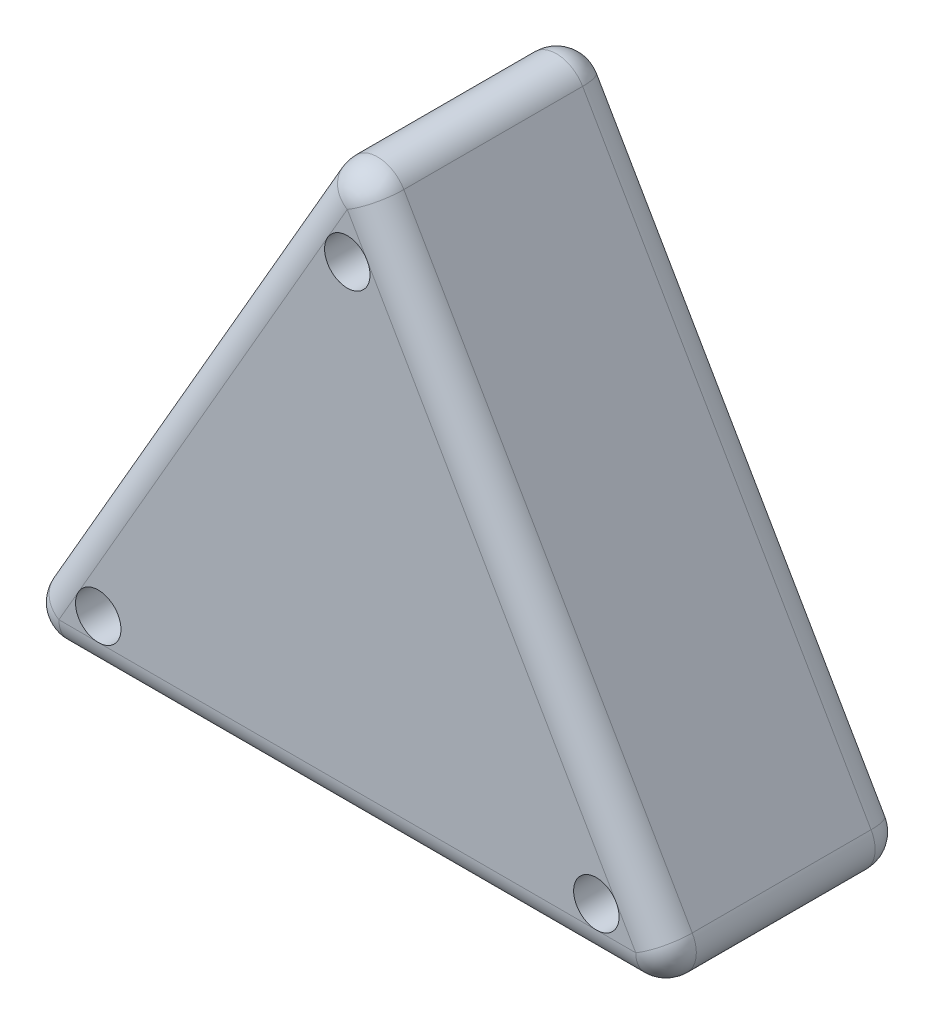
SolidWorks part; units mm, degrees
ref_plane "Plan de face" through (0, 0, 0) normal (0, 0, 1) x (1, 0, 0)
ref_plane "Plan de dessus" through (0, 0, 0) normal (0, 1, 0) x (1, 0, 0)
ref_plane "Plan de droite" through (0, 0, 0) normal (1, 0, 0) x (0, 0, -1)
sketch "Esquisse1" plane through (0, 0, 0) normal (0, 0, 1) x (1, 0, 0)
  line L0 (1.7321, 3) -> (20.7679, 35.9711)
  line L1 (3.4641, 0) -> (41.5359, 0)
  line L2 (24.2321, 35.9711) -> (43.2679, 3)
  line L3 (43.2679, 1) -> (31.5561, 7.7618) construction
  line L4 (22.5, 3.8637) -> (22.5, -6.3721) construction
  arc A0 (41.5359, 0) -> (43.2679, 3) centre (41.5359, 2) ccw
  arc A1 (1.7321, 3) -> (3.4641, 0) centre (3.4641, 2) ccw
  arc A2 (20.7679, 35.9711) -> (24.2321, 35.9711) centre (22.5, 34.9711) cw
  circle A6 centre (22.5, 31.9711) radius 1.5
  circle A7 centre (38.9378, 3.5) radius 1.5
  circle A8 centre (6.0622, 3.5) radius 1.5
  point P6 (45, 0)
  point P9 (0, 0)
  point P12 (22.5, 38.9711)
  dimension "D4" = 2
  dimension "D5" = 3
  dimension "D7" = 3
  dimension "D9" = 3
  dimension "D1" = 60
  dimension "D2" = 45
  dimension "D3" = 45
  dimension "D8" = 3
extrude "Boss.-Extru.1" add sketch "Esquisse1" along normal blind 15.8 contours L2 A0 L1 A1 L0 A2 | A8 | A7 | A6
sketch "Esquisse2" plane through (0, 0, 0) normal (0, 0, -1) x (-1, 0, 0)
  line L0 (-22.5, 31.9711) -> (-22.5, -6.8886) construction
  line L1 (-38.9378, 3.5) -> (-11.25, 19.4856) construction
  line L2 (-1.7321, 3) -> (-20.7679, 35.9711) construction
  circle A0 centre (-22.5, 12.9904) radius 9.01
  dimension "D1" = 18.02
extrude "Enlèv. mat.-Extru.1" cut sketch "Esquisse2" against normal blind 9.8
chamfer "Chanfrein1" distance 1 angle 45 1 edges at (13.49, 12.9904, 0)
fillet "Congé2" radius 2 12 edges at (1.7321, 1, 15.8) (22.5, 0, 15.8) (43.2679, 1, 15.8) (33.75, 19.4856, 15.8) (22.5, 36.9711, 15.8) (11.25, 19.4856, 15.8) (1.7321, 1, 0) (22.5, 0, 0) (43.2679, 1, 0) (33.75, 19.4856, 0) (22.5, 36.9711, 0) (11.25, 19.4856, 0)
